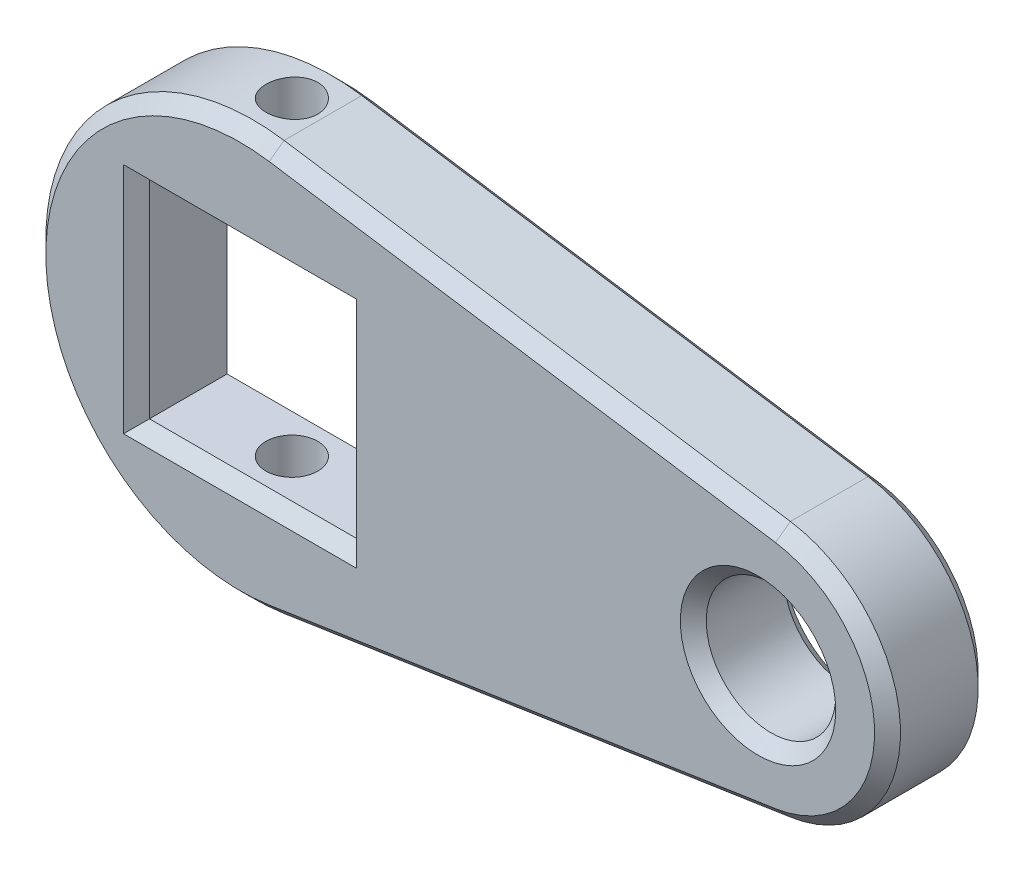
SolidWorks part; units mm, degrees
material "6061-T6 (GB)"
ref_plane "前视" through (0, 0, 0) normal (0, 0, 1) x (1, 0, 0)
ref_plane "上视" through (0, 0, 0) normal (0, 1, 0) x (1, 0, 0)
ref_plane "右视" through (0, 0, 0) normal (1, 0, 0) x (0, 0, -1)
sketch "草图1" plane through (0, 0, 0) normal (0, 0, 1) x (1, 0, 0)
  line L0 (0, 0) -> (41.6683, 0) construction
  line L1 (1.2, 7.9095) -> (20.75, 4.9434)
  line L2 (4, -4) -> (-4, -4)
  line L3 (4, -4) -> (4, 4)
  line L4 (4, 4) -> (-4, 4)
  line L5 (-4, -4) -> (-4, 4)
  line L6 (4, -4) -> (-4, 4) construction
  line L7 (4, 4) -> (-4, -4) construction
  line L8 (1.2, -7.9095) -> (20.75, -4.9434)
  arc A0 (1.2, 7.9095) -> (1.2, -7.9095) centre (0, 0) ccw
  circle A1 centre (20, 0) radius 2.5
  arc A2 (20.75, -4.9434) -> (20.75, 4.9434) centre (20, 0) ccw
  dimension "D1" = 8
  dimension "D2" = 8
  dimension "D3" = 20
  dimension "D4" = 5
  dimension "D5" = 5
extrude "凸台-拉伸1" add sketch "草图1" along normal mid plane 4
sketch "草图2" plane through (0, 0, 0) normal (0, 1, 0) x (1, 0, 0)
  circle A0 centre (0, 0) radius 1
  dimension "D1" = 2
extrude "切除-拉伸1" cut sketch "草图2" against normal mid plane 44
chamfer "倒角1" distance 0.5 angle 45 18 edges at (22.5, 0, -2) (0, 4, -2) (4, 0, -2) (0, -4, -2) (-4, 0, -2) (10.975, 6.4265, -2) (-8, 0, -2) (10.975, -6.4265, -2) (25, 0, -2) (22.5, 0, 2) (10.975, -6.4265, 2) (-8, 0, 2) (10.975, 6.4265, 2) (25, 0, 2) (4, 0, 2) (0, 4, 2) (-4, 0, 2) (0, -4, 2)
